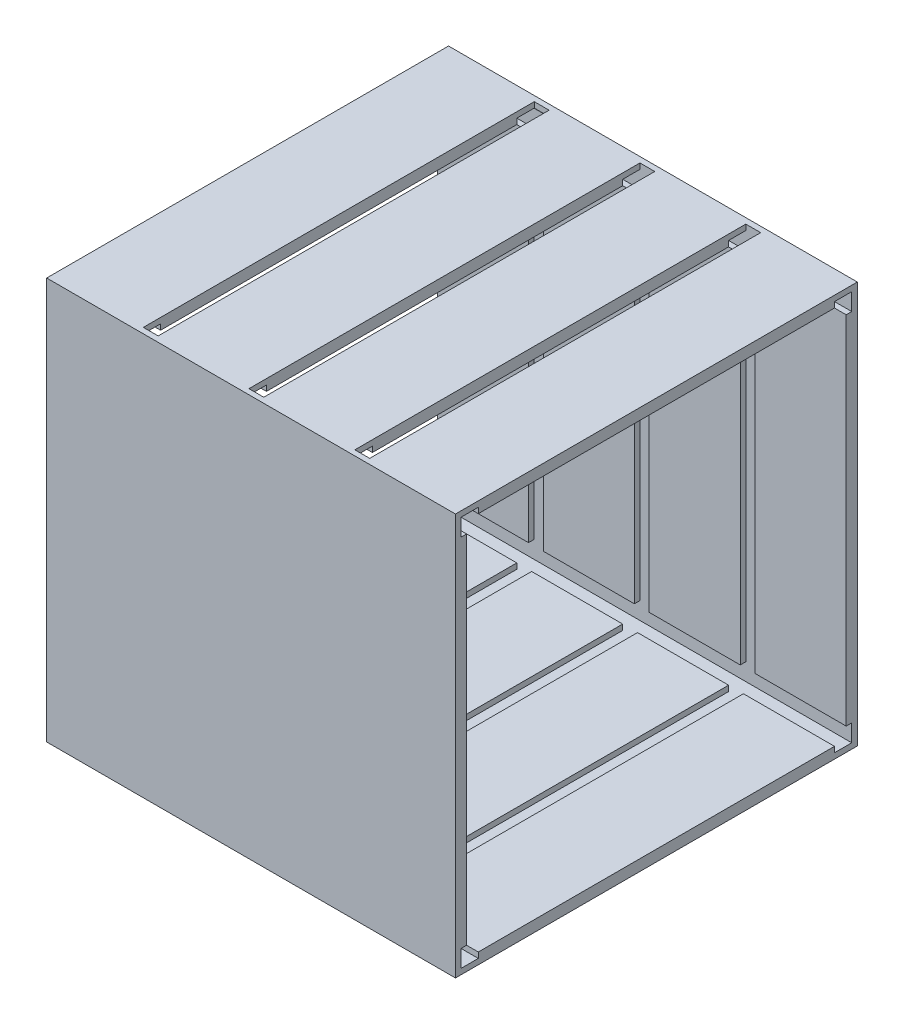
SolidWorks part; units mm, degrees
ref_plane "Front Plane" through (0, 0, 0) normal (0, 0, 1) x (1, 0, 0)
ref_plane "Top Plane" through (0, 0, 0) normal (0, 1, 0) x (1, 0, 0)
ref_plane "Right Plane" through (0, 0, 0) normal (1, 0, 0) x (0, 0, -1)
sketch "Sketch1" plane through (0, 0, 0) normal (1, 0, 0) x (0, 0, -1)
  line L1 (0, 0) -> (688.1, 0)
  line L2 (0, 0) -> (0, 688.1)
  line L3 (0, 688.1) -> (688.1, 688.1)
  line L4 (688.1, 0) -> (688.1, 688.1)
  line L5 (0, 0) -> (19.05, 0) construction
  line L6 (0, 0) -> (0, 19.05) construction
  line L7 (0, 19.05) -> (19.05, 19.05) construction
  line L8 (19.05, 0) -> (19.05, 19.05) construction
  line L9 (19.05, 19.05) -> (669.05, 19.05)
  line L10 (19.05, 19.05) -> (19.05, 669.05)
  line L11 (19.05, 669.05) -> (669.05, 669.05)
  line L12 (669.05, 19.05) -> (669.05, 669.05)
  dimension "D1" = 688.1
  dimension "D2" = 688.1
  dimension "D3" = 19.05
  dimension "D4" = 19.05
  dimension "D5" = 650
  dimension "D6" = 650
extrude "Boss-Extrude1" add sketch "Sketch1" along normal blind 700 contours L10 L11 L12 L9 | L2 L3 L4 L1
sketch "Sketch3" plane through (0, 0, -669.05) normal (0, 0, 1) x (1, 0, 0)
  line L1 (0, 669.05) -> (155.95, 669.05) construction
  line L2 (0, 669.05) -> (0, 19.05) construction
  line L3 (0, 19.05) -> (155.95, 19.05) construction
  line L4 (155.95, 669.05) -> (155.95, 19.05) construction
  line L5 (155.95, 669.05) -> (181.35, 669.05)
  line L6 (155.95, 669.05) -> (155.95, 19.05)
  line L7 (155.95, 19.05) -> (181.35, 19.05)
  line L8 (181.35, 669.05) -> (181.35, 19.05)
  line L9 (337.3, 669.05) -> (362.7, 669.05)
  line L10 (337.3, 669.05) -> (337.3, 19.05)
  line L11 (337.3, 19.05) -> (362.7, 19.05)
  line L12 (362.7, 669.05) -> (362.7, 19.05)
  line L13 (518.65, 669.05) -> (544.05, 669.05)
  line L14 (518.65, 669.05) -> (518.65, 19.05)
  line L15 (518.65, 19.05) -> (544.05, 19.05)
  line L16 (544.05, 669.05) -> (544.05, 19.05)
  line L17 (700, 688.1) -> (0, 688.1) construction
  point P15 (350, 669.05)
  dimension "D1" = 155.95
  dimension "D2" = 650
  dimension "D3" = 25.4
  dimension "D4" = 25.4
  dimension "D5" = 650
  dimension "D6" = 155.95
  dimension "D7" = 25.4
  dimension "D8" = 650
  dimension "D9" = 155.95
  dimension "D10" = 19.05
  dimension "D11" = 19.05
extrude "Cut-Extrude1" cut sketch "Sketch3" against normal blind 9.525
ref_plane "Plane1" through (0, 0, -344.05) normal (0, 0, -1) x (-1, 0, 0)
mirror "Mirror2" about plane through (0, 0, -344.05) normal (0, 0, -1) of "Cut-Extrude1"
ref_plane "Plane2" through (0, 344.05, 0) normal (0, 1, 0) x (1, 0, 0)
sketch "Sketch4" plane through (0, 19.05, 0) normal (0, 1, 0) x (1, 0, 0)
  line L0 (700, 688.1) -> (0, 688.1) construction
  line L1 (155.95, 678.575) -> (181.35, 678.575)
  line L2 (155.95, 678.575) -> (155.95, 9.075)
  line L3 (155.95, 9.075) -> (181.35, 9.075)
  line L4 (181.35, 678.575) -> (181.35, 9.075)
  line L5 (0, 0) -> (0, 688.1) construction
  line L6 (700, 0) -> (0, 0) construction
  line L7 (337.3, 678.575) -> (362.7, 678.575)
  line L8 (337.3, 678.575) -> (337.3, 9.075)
  line L9 (337.3, 9.075) -> (362.7, 9.075)
  line L10 (362.7, 678.575) -> (362.7, 9.075)
  line L11 (518.65, 678.575) -> (544.05, 678.575)
  line L12 (518.65, 678.575) -> (518.65, 9.525)
  line L13 (518.65, 9.525) -> (544.05, 9.525)
  line L14 (544.05, 678.575) -> (544.05, 9.525)
  dimension "D1" = 25.4
  dimension "D2" = 669.5
  dimension "D3" = 9.525
  dimension "D4" = 155.95
  dimension "D5" = 669.5
  dimension "D6" = 25.4
  dimension "D7" = 9.525
  dimension "D8" = 155.95
  dimension "D9" = 25.4
  dimension "D10" = 155.95
  dimension "D11" = 9.525
  dimension "D12" = 9.525
extrude "Cut-Extrude3" cut sketch "Sketch4" against normal blind 9.525
mirror "Mirror4" about plane through (0, 344.05, 0) normal (0, 1, 0) of "Cut-Extrude3"
sketch "Sketch6" plane through (0, 688.1, 0) normal (0, 1, 0) x (1, 0, 0)
  line L0 (0, 0) -> (0, 688.1) construction
  line L1 (155.95, 679.025) -> (181.35, 679.025)
  line L2 (155.95, 679.025) -> (155.95, 9.525)
  line L3 (155.95, 9.525) -> (181.35, 9.525)
  line L4 (181.35, 679.025) -> (181.35, 9.525)
  line L5 (337.3, 678.575) -> (362.7, 678.575)
  line L6 (337.3, 678.575) -> (337.3, 9.075)
  line L7 (337.3, 9.075) -> (362.7, 9.075)
  line L8 (362.7, 678.575) -> (362.7, 9.075)
  line L9 (518.65, 678.575) -> (544.05, 678.575)
  line L10 (518.65, 678.575) -> (518.65, 9.075)
  line L11 (518.65, 9.075) -> (544.05, 9.075)
  line L12 (544.05, 678.575) -> (544.05, 9.075)
  line L13 (700, 0) -> (0, 0) construction
  line L14 (700, 688.1) -> (0, 688.1) construction
  dimension "D1" = 669.5
  dimension "D2" = 25.4
  dimension "D3" = 155.95
  dimension "D4" = 9.525
  dimension "D5" = 25.4
  dimension "D6" = 669.5
  dimension "D7" = 9.525
  dimension "D8" = 155.95
  dimension "D9" = 25.4
  dimension "D10" = 669.5
  dimension "D11" = 9.525
  dimension "D12" = 155.95
extrude "Cut-Extrude4" cut sketch "Sketch6" against normal blind 9.525
sketch "Sketch7" plane through (0, 0, 0) normal (-1, 0, 0) x (0, 0, 1)
  line L0 (-19.05, 39.05) -> (-9.525, 39.05)
  line L1 (-19.05, 19.05) -> (-19.05, 669.05) construction
  line L2 (-9.525, 39.05) -> (-9.525, 9.525)
  line L3 (-9.525, 9.525) -> (-39.05, 9.525)
  line L4 (-39.05, 9.525) -> (-39.05, 19.05)
  line L5 (-19.05, 19.05) -> (-669.05, 19.05) construction
  line L6 (-39.05, 19.05) -> (-19.05, 19.05)
  line L7 (-19.05, 19.05) -> (-19.05, 39.05)
  dimension "D1" = 9.525
  dimension "D2" = 20
  dimension "D3" = 20
  dimension "D4" = 9.525
extrude "Cut-Extrude5" cut sketch "Sketch7" against normal blind 700
mirror "Mirror5" about plane through (0, 0, -344.05) normal (0, 0, -1) of "Cut-Extrude5"
mirror "Mirror6" about plane through (0, 344.05, 0) normal (0, 1, 0) of "Mirror5"
